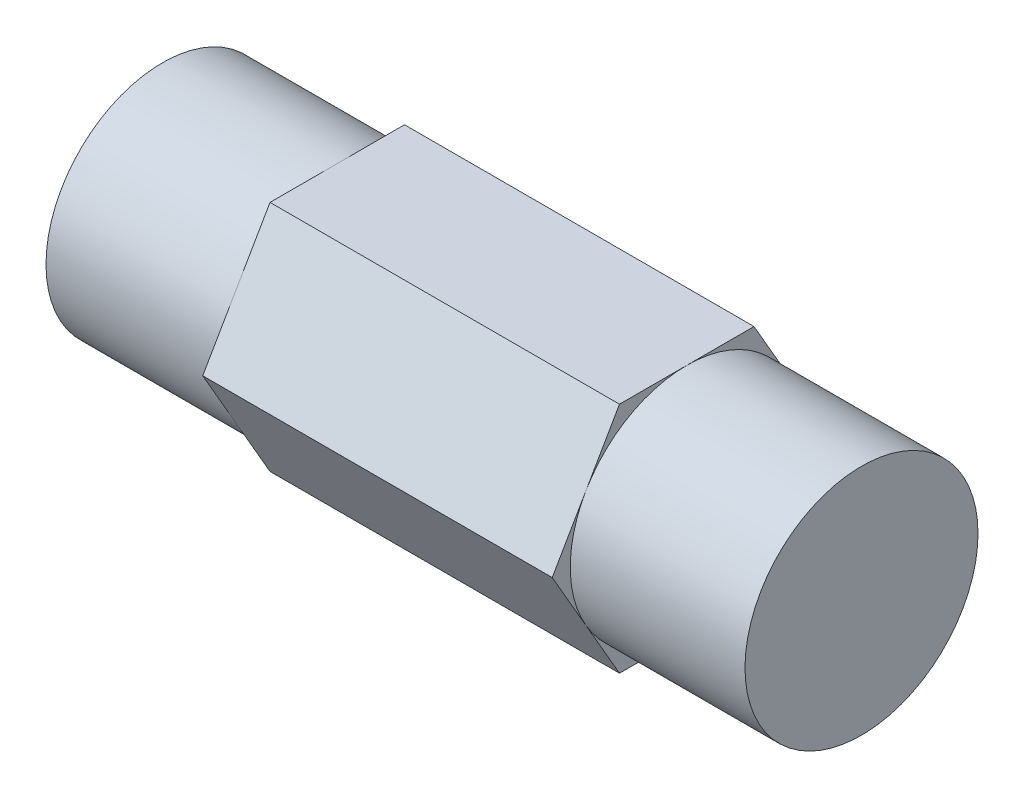
SolidWorks part; units mm, degrees
material "6061-T6 (SS)"
ref_plane "Front Plane" through (0, 0, 0) normal (0, 0, 1) x (1, 0, 0)
ref_plane "Top Plane" through (0, 0, 0) normal (0, 1, 0) x (1, 0, 0)
ref_plane "Right Plane" through (0, 0, 0) normal (1, 0, 0) x (0, 0, -1)
sketch "Sketch1" plane through (0, 0, 0) normal (1, 0, 0) x (0, 0, -1)
  line L1 (-3.6662, -6.35) -> (3.6662, -6.35)
  line L2 (3.6662, -6.35) -> (7.3323, 0)
  line L3 (7.3323, 0) -> (3.6662, 6.35)
  line L4 (3.6662, 6.35) -> (-3.6662, 6.35)
  line L5 (-3.6662, 6.35) -> (-7.3323, 0)
  line L6 (-7.3323, 0) -> (-3.6662, -6.35)
  circle A0 centre (0, 0) radius 6.35 construction
  dimension "D1" = 12.7
extrude "Boss-Extrude1" add sketch "Sketch1" along normal blind 19.05
sketch "Sketch2" plane through (19.05, 0, 0) normal (1, 0, 0) x (0, 0, -1)
  circle A0 centre (0, 0) radius 6.35
  dimension "D1" = 12.7
extrude "Boss-Extrude2" add sketch "Sketch2" along normal blind 9.525
sketch "Sketch3" plane through (0, 0, 0) normal (-1, 0, 0) x (0, 0, 1)
  circle A0 centre (0, 0) radius 6.35
  dimension "D1" = 12.7
extrude "Boss-Extrude3" add sketch "Sketch3" along normal blind 9.525
